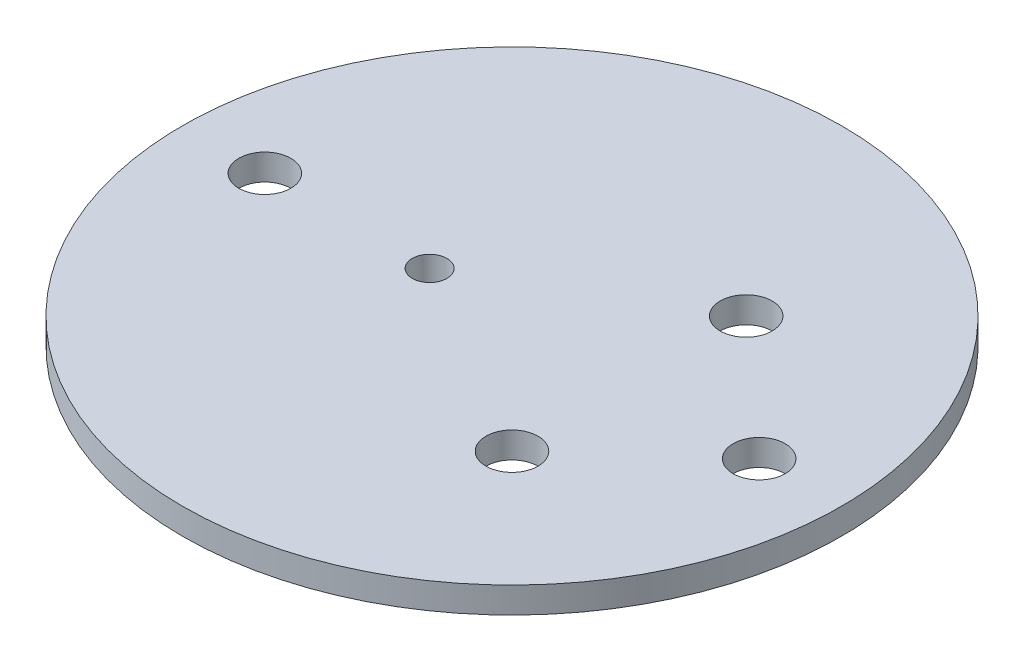
SolidWorks part; units mm, degrees
ref_plane "Front Plane" through (0, 0, 0) normal (0, 0, 1) x (1, 0, 0)
ref_plane "Top Plane" through (0, 0, 0) normal (0, 1, 0) x (1, 0, 0)
ref_plane "Right Plane" through (0, 0, 0) normal (1, 0, 0) x (0, 0, -1)
sketch "Sketch1" plane through (0, 0, 0) normal (0, 1, 0) x (1, 0, 0)
  line L0 (-28.5, 0) -> (28.5, 0) construction
  line L1 (13.5, 0) -> (13.5, 13.5)
  line L2 (13.5, 0) -> (13.5, -13.5)
  circle A1 centre (28.5, 0) radius 3
  circle A2 centre (-28.5, 0) radius 3
  circle A3 centre (13.5, 13.5) radius 3
  circle A4 centre (13.5, -13.5) radius 3
  circle A5 centre (-28.5, 0) radius 6.25 construction
  circle A6 centre (13.5, 13.5) radius 12.5 construction
  circle A7 centre (13.5, -13.5) radius 12.5 construction
  circle A8 centre (28.5, 0) radius 6.25 construction
  circle A9 centre (0, 0) radius 38
  circle A10 centre (-9.5, 0) radius 2
  circle A11 centre (-9.5, 0) radius 12.5 construction
  point P11 (0, 0)
  dimension "D1" = 76
  dimension "D3" = 6
  dimension "D4" = 13.5
  dimension "D5" = 6
  dimension "D6" = 12.5
  dimension "D7" = 25
  dimension "D8" = 4
  dimension "D9" = 25
  dimension "D2" = 57
  dimension "D10" = 9.5
  dimension "D11" = 13.5
extrude "Boss-Extrude1" add sketch "Sketch1" against normal blind 3 contours A4 A3 A2 A1 region at (-0.146, 0, 0)
